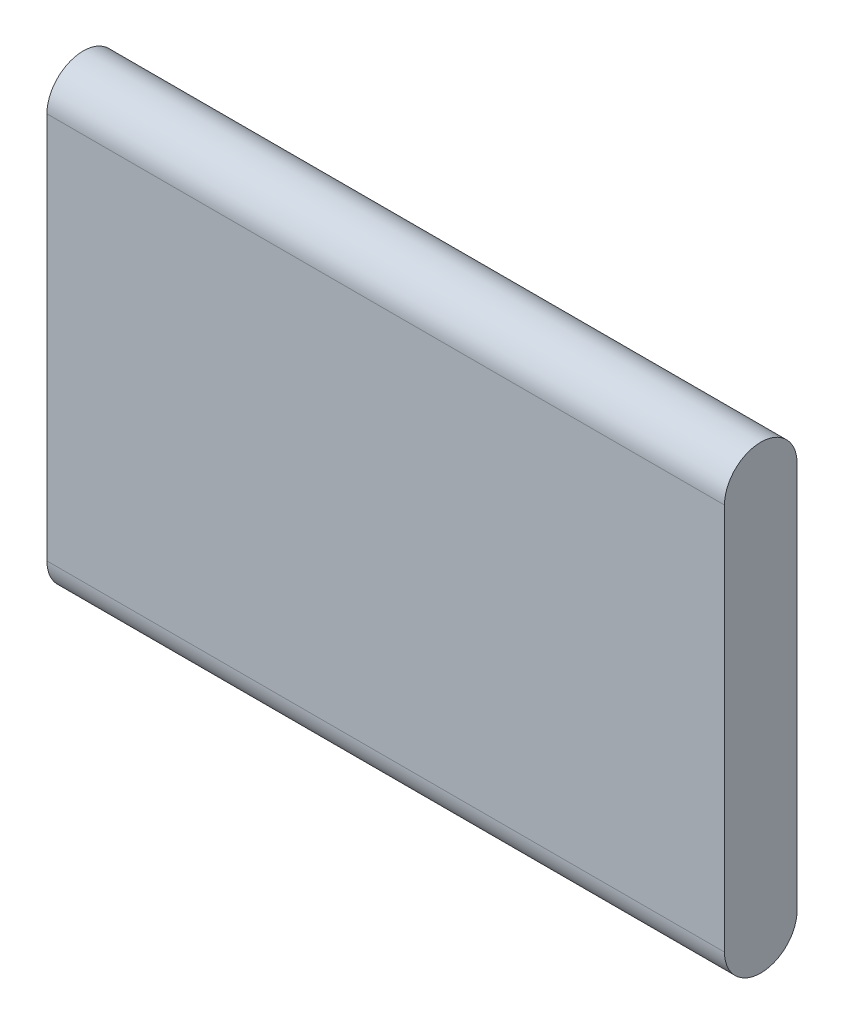
SolidWorks part; units mm, degrees
ref_plane "Front Plane" through (0, 0, 0) normal (0, 0, 1) x (1, 0, 0)
ref_plane "Top Plane" through (0, 0, 0) normal (0, 1, 0) x (1, 0, 0)
ref_plane "Right Plane" through (0, 0, 0) normal (1, 0, 0) x (0, 0, -1)
sketch "Sketch1" plane through (0, 0, 0) normal (1, 0, 0) x (0, 0, -1)
  line L0 (-38.1, 203.2) -> (38.1, -203.2) construction
  line L2 (-38.1, 203.2) -> (-38.1, -203.2)
  line L4 (38.1, 203.2) -> (38.1, -203.2)
  arc A0 (38.1, 203.2) -> (-38.1, 203.2) centre (0, 203.2) ccw
  arc A1 (-38.1, -203.2) -> (38.1, -203.2) centre (0, -203.2) ccw
  dimension "D1" = 38.1
  dimension "D2" = 482.6
extrude "Boss-Extrude1" add sketch "Sketch1" along normal mid plane 711.2
